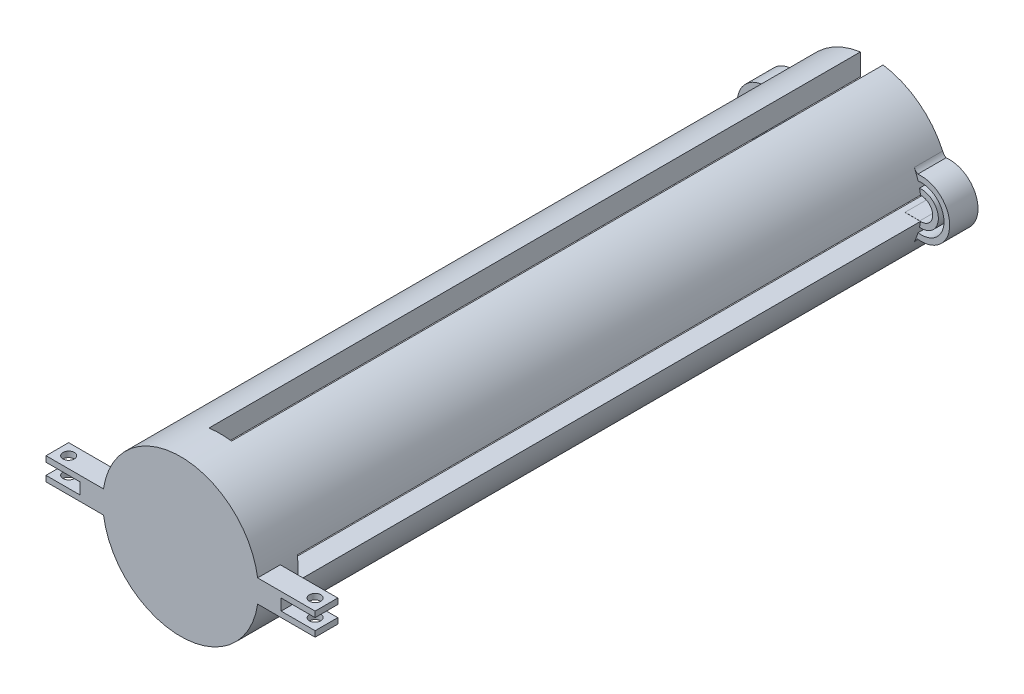
SolidWorks part; units mm, degrees
ref_plane "Front Plane" through (0, 0, 0) normal (0, 0, 1) x (1, 0, 0)
ref_plane "Top Plane" through (0, 0, 0) normal (0, 1, 0) x (1, 0, 0)
ref_plane "Right Plane" through (0, 0, 0) normal (1, 0, 0) x (0, 0, -1)
sketch "Sketch1" plane through (0, 0, 0) normal (0, 0, 1) x (1, 0, 0)
  circle A0 centre (0, 0) radius 12.7
  dimension "D1" = 25.4
extrude "Extrude-Thin1" add sketch "Sketch1" along normal blind 152.4 thin thin type one direction wall 4.7625
ref_plane "Plane1" through (0, 0, 6.35) normal (0, 0, -1) x (-1, 0, 0)
sketch "Sketch2" plane through (0, 0, 6.35) normal (0, 0, -1) x (-1, 0, 0)
  line L0 (-2.54, 2.54) -> (-31.75, 2.54)
  line L1 (2.54, 31.75) -> (-2.54, 31.75)
  line L2 (2.54, 31.75) -> (2.54, 2.54)
  line L3 (2.54, -31.75) -> (-2.54, -31.75)
  line L4 (-2.54, 31.75) -> (-2.54, 2.54)
  line L5 (2.54, 31.75) -> (-2.54, -31.75) construction
  line L6 (2.54, -31.75) -> (-2.54, 31.75) construction
  line L7 (31.75, 2.54) -> (2.54, 2.54)
  line L8 (31.75, 2.54) -> (31.75, -2.54)
  line L9 (31.75, -2.54) -> (2.54, -2.54)
  line L10 (-31.75, 2.54) -> (-31.75, -2.54)
  line L11 (31.75, 2.54) -> (-31.75, -2.54) construction
  line L12 (31.75, -2.54) -> (-31.75, 2.54) construction
  line L15 (2.54, -2.54) -> (2.54, -31.75)
  line L17 (-2.54, -2.54) -> (-31.75, -2.54)
  line L18 (-2.54, -2.54) -> (-2.54, -31.75)
  point P0 (0, 0)
  point P6 (0, 0)
  dimension "D1" = 5.08
  dimension "D2" = 5.08
  dimension "D3" = 63.5
  dimension "D4" = 63.5
  dimension "D5" = 2.54
  dimension "D6" = 2.54
  dimension "D7" = 29.21
  dimension "D8" = 29.21
extrude "Cut-Extrude1" cut sketch "Sketch2" against normal blind 139.7 and the other way blind 25.4
sketch "Sketch3" plane through (0, 0, 0) normal (0, 0, 1) x (1, 0, 0)
  line L0 (-17.4625, 0) -> (17.4625, 0) construction
  line L1 (16.7236, 5.026) -> (15.0811, 5.026)
  line L2 (15.0811, 5.026) -> (15.0811, 3.7873)
  line L3 (15.0811, 3.7873) -> (17.0469, 3.7873)
  line L4 (-16.7236, 5.026) -> (-15.5724, 5.026)
  line L5 (-15.5724, 5.026) -> (-15.5724, 3.7873)
  line L6 (-15.5724, 3.7873) -> (-17.0469, 3.7873)
  line L7 (-17.0469, -3.7873) -> (-15.5724, -3.7873)
  line L8 (-15.5724, -3.7873) -> (-15.5724, -5.026)
  line L9 (-15.5724, -5.026) -> (-16.7236, -5.026)
  line L10 (17.0469, -3.7873) -> (15.0811, -3.7873)
  line L11 (15.0811, -3.7873) -> (15.0811, -5.026)
  line L12 (15.0811, -5.026) -> (16.7236, -5.026)
  circle A0 centre (0, 0) radius 17.4625 construction
  arc A1 (17.0469, 3.7873) -> (17.0469, -3.7873) centre (17.4625, 0) cw
  circle A2 centre (0, 0) radius 17.4625 construction
  arc A3 (-17.0469, 3.7873) -> (-17.0469, -3.7873) centre (-17.4625, 0) ccw
  arc A4 (16.7236, 5.026) -> (16.7236, -5.026) centre (17.4625, 0) cw
  arc A5 (17.2768, 2.54) -> (2.54, 17.2768) centre (0, 0) ccw construction
  arc A6 (2.54, -17.2768) -> (17.2768, -2.54) centre (0, 0) ccw construction
  arc A7 (-16.7236, 5.026) -> (-16.7236, -5.026) centre (-17.4625, 0) ccw
  arc A8 (-2.54, 17.2768) -> (-17.2768, 2.54) centre (0, 0) ccw construction
  arc A9 (-17.2768, -2.54) -> (-2.54, -17.2768) centre (0, 0) ccw construction
  dimension "D1" = 3.81
  dimension "D2" = 3.81
  dimension "D3" = 5.08
  dimension "D4" = 5.08
  dimension "D5" = 1.9657
  dimension "D6" = 1.9657
  dimension "D7" = 1.4745
  dimension "D8" = 1.4745
extrude "Extrude-Thin2" add sketch "Sketch3" along normal blind 6.35 thin thin type one direction wall 1.27
sketch "Sketch4" plane through (0, 0, 152.4) normal (0, 0, 1) x (1, 0, 0)
  circle A0 centre (0, 0) radius 17.4625
  dimension "D1" = 34.925
extrude "Boss-Extrude1" add sketch "Sketch4" along normal blind 2.54
fillet "Fillet1" radius 2.54 4 edges at (-16.288, -6.296, 3.175) (-16.288, 6.296, 3.175) (16.288, -6.296, 3.175) (16.288, 6.296, 3.175)
ref_plane "Plane3" through (17.4625, 0, 146.05) normal (1, 0, 0) x (0, 0, -1)
sketch "Sketch5" plane through (17.4625, 0, 146.05) normal (1, 0, 0) x (0, 0, -1)
  line L0 (-8.89, 17.4625) -> (-8.89, -17.4625) construction
  line L1 (-8.89, 2.54) -> (-3.81, 2.54)
  line L2 (-8.89, 2.54) -> (-8.89, -2.54)
  line L3 (-8.89, -2.54) -> (-3.81, -2.54)
  line L4 (-3.81, 2.54) -> (-3.81, -2.54)
  line L5 (-8.89, 2.54) -> (-3.81, -2.54) construction
  line L6 (-8.89, -2.54) -> (-3.81, 2.54) construction
  line L8 (0, -2.54) -> (0, 2.54) construction
  point P0 (-6.35, 0)
  point P8 (0, 0)
  dimension "D1" = 5.08
  dimension "D2" = 5.08
  dimension "D3" = 2.54
extrude "Boss-Extrude2" add sketch "Sketch5" along normal blind 12.7 and the other way up to next (4.7625 mm away)
sketch "Sketch6" plane through (0, 0, 154.94) normal (0, 0, 1) x (1, 0, 0)
  line L0 (30.1625, 2.54) -> (30.1625, -2.54) construction
  line L1 (22.5425, 1.27) -> (30.1625, 1.27)
  line L2 (22.5425, 1.27) -> (22.5425, -1.27)
  line L3 (22.5425, -1.27) -> (30.1625, -1.27)
  line L4 (30.1625, 1.27) -> (30.1625, -1.27)
  line L5 (22.5425, 1.27) -> (30.1625, -1.27) construction
  line L6 (22.5425, -1.27) -> (30.1625, 1.27) construction
  point P0 (26.3525, 0)
  point P7 (30.1625, 0)
  dimension "D1" = 2.54
  dimension "D2" = 7.62
extrude "Cut-Extrude2" cut sketch "Sketch6" against normal up to next
sketch "Sketch7" plane through (0, -2.54, 0) normal (0, -1, 0) x (1, 0, 0)
  line L0 (30.1625, 154.94) -> (30.1625, 149.86) construction
  circle A0 centre (27.6225, 152.4) radius 1.27
  point P4 (30.1625, 152.4)
  dimension "D1" = 2.54
  dimension "D2" = 2.54
extrude "Cut-Extrude3" cut sketch "Sketch7" against normal through all
mirror "Mirror2" about plane through (0, 0, 0) normal (1, 0, 0) of "Cut-Extrude3", "Cut-Extrude2", "Boss-Extrude2"
